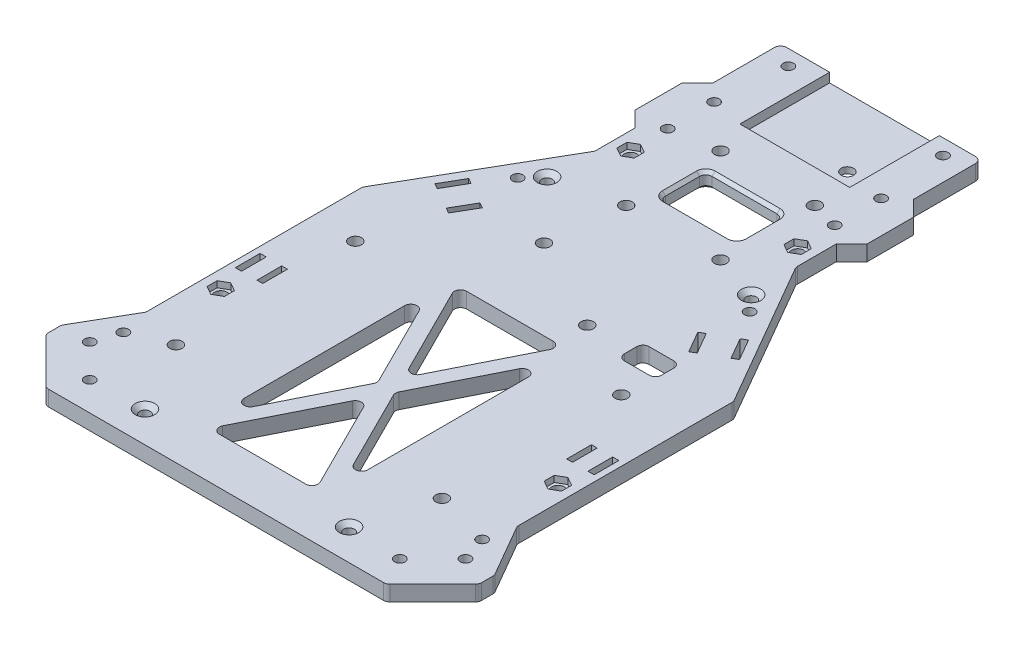
SolidWorks part; units mm, degrees
material "ABS PC"
ref_plane "Front Plane" through (0, 0, 0) normal (0, 0, 1) x (1, 0, 0)
ref_plane "Top Plane" through (0, 0, 0) normal (0, 1, 0) x (1, 0, 0)
ref_plane "Right Plane" through (0, 0, 0) normal (1, 0, 0) x (0, 0, -1)
sketch "Sketch1" plane through (0, 0, 0) normal (0, 1, 0) x (1, 0, 0)
  line L1 (70, -110) -> (-70, -110)
  line L2 (70, -110) -> (70, 110)
  line L3 (70, 110) -> (-70, 110)
  line L4 (-70, -110) -> (-70, 110)
  line L5 (70, -110) -> (-70, 110) construction
  line L6 (70, 110) -> (-70, -110) construction
  point P0 (0, 0)
  dimension "D1" = 220
  dimension "D2" = 140
extrude "Boss-Extrude1" add sketch "Sketch1" along normal blind 5
sketch "FC Mounting Holes" plane through (0, 5, 0) normal (0, 1, 0) x (1, 0, 0)
  line L0 (0, 110) -> (0, -110) construction
  line L1 (70, 110) -> (-70, 110) construction
  line L2 (-70, -110) -> (70, -110) construction
  line L4 (18.25, 65.325) -> (-12.25, 65.325) construction
  line L5 (18.25, 65.325) -> (18.25, 34.825) construction
  line L6 (18.25, 34.825) -> (-12.25, 34.825) construction
  line L7 (-12.25, 65.325) -> (-12.25, 34.825) construction
  line L8 (18.25, 65.325) -> (-12.25, 34.825) construction
  line L9 (18.25, 34.825) -> (-12.25, 65.325) construction
  point P6 (3, 50.075)
  dimension "D1" = 30.5
  dimension "D2" = 60
  dimension "D3" = 3
hole_wizard "Ø4.0 (4) Diameter Hole1" positions "Sketch3" profile "Sketch4" hole size "Ø4.0" standard "ANSI Metric" end condition through all
sketch "Sketch3" plane through (0, 5, 0) normal (0, 1, 0) x (1, 0, 0)
  point P0 (-12.25, 34.825)
  point P3 (-12.25, 65.325)
  point P6 (18.25, 65.325)
  point P9 (18.25, 34.825)
sketch "Sketch4" plane through (-12.25, 5, -34.825) normal (1, 0, 0) x (0, 0, 1)
  line L0 (0, 0) -> (0, 5)
  line L1 (0, 5) -> (2, 5)
  line L2 (2, 5) -> (2, 0)
  line L5 (2, 0) -> (0, 0)
  line L11 (0, -6.35) -> (0, 107.95) construction
  dimension "Thru Hole Dia." = 4
  dimension "Thru Hole Depth" = 5
sketch "Sketch8" plane through (0, 5, 0) normal (0, 1, 0) x (1, 0, 0)
  line L0 (-70, 110) -> (-32.5, 110)
  line L1 (70, 110) -> (-70, 110) construction
  line L2 (-32.5, 110) -> (-32.5, 44.9519)
  line L3 (-32.5, 44.9519) -> (-70, -20)
  line L4 (-70, 110) -> (-70, -110) construction
  line L5 (-70, 110) -> (-70, -20)
  line L6 (0, 110) -> (0, -110) construction
  line L7 (-70, -110) -> (70, -110) construction
  line L8 (70, 110) -> (70, -20)
  line L9 (32.5, 44.9519) -> (70, -20)
  line L10 (32.5, 110) -> (32.5, 44.9519)
  line L11 (70, 110) -> (32.5, 110)
  dimension "D1" = 130
  dimension "D2" = 30
  dimension "D3" = 65
extrude "Cut-Extrude1" cut sketch "Sketch8" against normal blind 5
chamfer "Chamfer3" distance 15 angle 45 2 edges at (70, 2.5, 110) (-70, 2.5, 110)
sketch "Sketch10" plane through (0, 0, 0) normal (0, 1, 0) x (1, 0, 0)
  line L0 (0, 110) -> (0, -110) construction
  line L1 (32.5, 110) -> (-32.5, 110) construction
  line L2 (-55, -110) -> (55, -110) construction
  line L3 (-27, 78) -> (-27, 63) construction
  line L4 (-62.5, -102.5) -> (-55.4289, -95.4289) construction
  line L5 (-60.7322, -90.1256) -> (-50.1256, -100.7322) construction
  line L6 (-70, -95) -> (-55, -110) construction
  point P9 (27, 63)
  point P10 (27, 78)
  point P17 (50.1256, -100.7322)
  point P18 (60.7322, -90.1256)
  dimension "D1" = 15
  dimension "D2" = 27
  dimension "D3" = 32
  dimension "D4" = 15
  dimension "D5" = 10
sketch "Sketch15" plane through (0, 5, 0) normal (0, 1, 0) x (1, 0, 0)
  line L0 (0, 110) -> (0, -110) construction
  line L1 (32.5, 110) -> (-32.5, 110) construction
  line L2 (-55, -110) -> (55, -110) construction
  line L3 (25, 100) -> (-25, 100) construction
  line L4 (37.5, 25) -> (-37.5, 25) construction
  line L5 (34, -50) -> (-34, -50) construction
  point P9 (0, 100)
  point P13 (0, 25)
  point P15 (0, -50)
  dimension "D1" = 50
  dimension "D2" = 10
  dimension "D3" = 75
  dimension "D4" = 85
  dimension "D5" = 68
  dimension "D6" = 160
hole_wizard "CSK for M3 Flat Head Machine Screw4" positions "Sketch16" profile "Sketch17" countersink size "M3" standard "ANSI Metric"
sketch "Sketch16" plane through (0, 0, 0) normal (0, 1, 0) x (1, 0, 0)
  point P6 (37.5, 25)
  point P9 (-37.5, 25)
  point P12 (-25, 100)
  point P15 (25, 100)
sketch "Sketch17" plane through (37.5, 0, -25) normal (1, 0, 0) x (0, 0, -1)
  line L0 (0, 0) -> (0, 6.0215)
  line L1 (0, 6.0215) -> (1.7, 5)
  line L2 (1.7, 5) -> (1.7, 1.45)
  line L3 (1.7, 1.45) -> (3.15, 0)
  line L5 (3.15, 0) -> (0, 0)
  line L6 (-1.7, 1.45) -> (-3.15, 0) construction
  line L10 (0, 6.0215) -> (-1.7, 5) construction
  line L11 (0, -6.35) -> (0, 107.95) construction
  dimension "Hole Dia." = 3.4
  dimension "Hole Depth" = 5
  dimension "Near C'Sink Dia." = 6.3
  dimension "Near C'Sink Angle" = 90
  dimension "Drill Angle" = 118
sketch "Sketch18" plane through (0, 5, 0) normal (0, 1, 0) x (1, 0, 0)
  line L0 (32.5, 110) -> (-32.5, 110) construction
  line L1 (-54.3433, 120.6104) -> (40.6659, 120.6104)
  line L2 (-54.3433, 120.6104) -> (-54.3433, 105)
  line L3 (-54.3433, 105) -> (40.6659, 105)
  line L4 (40.6659, 120.6104) -> (40.6659, 105)
  dimension "D1" = 5
extrude "Cut-Extrude2" cut sketch "Sketch18" against normal blind 5
sketch "Sketch21" plane through (0, 0, 0) normal (0, -1, 0) x (1, 0, 0)
  line L0 (3, 96.3973) -> (3, -109.7164) construction
  line L1 (-9.0168, -65.325) -> (-10.6334, -62.525)
  line L2 (-10.6334, -62.525) -> (-13.8666, -62.525)
  line L3 (-13.8666, -62.525) -> (-15.4832, -65.325)
  line L4 (-15.4832, -65.325) -> (-13.8666, -68.125)
  line L5 (-13.8666, -68.125) -> (-10.6334, -68.125)
  line L6 (-10.6334, -68.125) -> (-9.0168, -65.325)
  line L7 (-12.25, -34.825) -> (-12.25, -65.325) construction
  line L8 (-4.8959, -50.075) -> (-19.6041, -50.075) construction
  line L9 (-10.6334, -32.025) -> (-9.0168, -34.825)
  line L10 (-13.8666, -32.025) -> (-10.6334, -32.025)
  line L11 (-15.4832, -34.825) -> (-13.8666, -32.025)
  line L12 (-13.8666, -37.625) -> (-15.4832, -34.825)
  line L13 (-10.6334, -37.625) -> (-13.8666, -37.625)
  line L14 (-9.0168, -34.825) -> (-10.6334, -37.625)
  line L29 (16.6334, -68.125) -> (15.0168, -65.325)
  line L30 (19.8666, -68.125) -> (16.6334, -68.125)
  line L31 (21.4832, -65.325) -> (19.8666, -68.125)
  line L32 (19.8666, -62.525) -> (21.4832, -65.325)
  line L33 (16.6334, -62.525) -> (19.8666, -62.525)
  line L34 (15.0168, -65.325) -> (16.6334, -62.525)
  line L35 (15.0168, -34.825) -> (16.6334, -37.625)
  line L36 (16.6334, -37.625) -> (19.8666, -37.625)
  line L37 (19.8666, -37.625) -> (21.4832, -34.825)
  line L38 (21.4832, -34.825) -> (19.8666, -32.025)
  line L39 (19.8666, -32.025) -> (16.6334, -32.025)
  line L40 (16.6334, -32.025) -> (15.0168, -34.825)
  circle A0 centre (-12.25, -65.325) radius 2.8 construction
  circle A2 centre (18.25, -65.325) radius 2.8 construction
  point P17 (-12.25, -50.075)
  dimension "D1" = 5.6
  dimension "D2" = 3
extrude "Cut-Extrude5" cut sketch "Sketch21" against normal blind 2
hole_wizard "CSK for M3 Flat Head Machine Screw3" positions "Sketch29" profile "Sketch30" countersink size "M3" standard "ANSI Metric" end condition through all
sketch "Sketch29" plane through (0, 0, 0) normal (0, 1, 0) x (1, 0, 0)
  line L0 (0, -17.8468) -> (0, 28.1017) construction
  line L2 (-70, -20) -> (-70, -95) construction
  line L3 (-55, -110) -> (55, -110) construction
  point P2 (-58, -82)
  point P10 (58, -82)
  dimension "D3" = 12
  dimension "D4" = 28
sketch "Sketch30" plane through (-58, 0, 82) normal (1, 0, 0) x (0, 0, -1)
  line L0 (0, 0) -> (0, 5)
  line L1 (0, 5) -> (1.7, 5)
  line L2 (1.7, 5) -> (1.7, 1.45)
  line L3 (1.7, 1.45) -> (3.15, 0)
  line L5 (3.15, 0) -> (0, 0)
  line L6 (-1.7, 1.45) -> (-3.15, 0) construction
  line L11 (0, -6.35) -> (0, 107.95) construction
  dimension "Thru Hole Dia." = 3.4
  dimension "Thru Hole Depth" = 5
  dimension "Near C'Sink Dia." = 6.3
  dimension "Near C'Sink Angle" = 90
sketch "Sketch32" plane through (0, 0, 0) normal (0, -1, 0) x (1, 0, 0)
  line L0 (-21.5, 12) -> (-21.5, 98) construction
  line L1 (-21.5, 98) -> (21.5, 98) construction
  line L2 (21.5, 98) -> (21.5, 12) construction
  line L3 (21.5, 12) -> (-21.5, 12) construction
  line L4 (-21.5, 12) -> (21.5, 98) construction
  line L5 (-20, 55) -> (20, 55) construction
  line L6 (20, 15) -> (-20, 15)
  line L7 (20, 15) -> (20, 95)
  line L8 (20, 95) -> (-20, 95)
  line L9 (-20, 15) -> (-20, 95)
  line L10 (20, 15) -> (-20, 95) construction
  line L11 (20, 95) -> (-20, 15) construction
  line L12 (0, 15) -> (0, 95) construction
  line L13 (-20, 20.5902) -> (-2.7951, 55)
  line L14 (-17.2049, 15) -> (0, 49.4098)
  line L15 (-11.4698, 26.4703) -> (-15.9419, 28.7064)
  line L16 (-17.2049, 95) -> (0, 60.5902)
  line L17 (-20, 89.4098) -> (-2.7951, 55)
  line L18 (17.2049, 15) -> (0, 49.4098)
  line L19 (17.2049, 95) -> (0, 60.5902)
  line L20 (20, 89.4098) -> (2.7951, 55)
  line L21 (20, 20.5902) -> (2.7951, 55)
  line L22 (-55, 110) -> (55, 110) construction
  point P8 (0, 55)
  point P25 (-13.7058, 27.5883)
  dimension "D1" = 3
  dimension "D2" = 5
  dimension "D3" = 80
  dimension "D4" = 40
  dimension "D5" = 55
extrude "Cut-Extrude10" cut sketch "Sketch32" against normal through all contours L19 L8 L16 | L17 L9 L13 | L21 L7 L20 | L6 L18 L14 region at (0, 0, 26.4699) region at (14.265, 0, 55) region at (-14.265, 0, 55) region at (0, 0, 83.5301)
fillet "Fillet1" radius 2 12 edges at (20, 2.5, 89.4098) (20, 2.5, 20.5902) (2.7951, 2.5, 55) (-17.2049, 2.5, 95) (17.2049, 2.5, 95) (0, 2.5, 60.5902) (-20, 2.5, 89.4098) (-2.7951, 2.5, 55) (-20, 2.5, 20.5902) (0, 2.5, 49.4098) (17.2049, 2.5, 15) (-17.2049, 2.5, 15)
sketch "Sketch33" plane through (0, 5, 0) normal (0, 1, 0) x (1, 0, 0)
  line L1 (-46, -77) -> (40, -77)
  line L2 (-46, -77) -> (-46, -19)
  line L3 (-46, -19) -> (40, -19)
  line L4 (40, -77) -> (40, -19)
  line L5 (-46, -77) -> (40, -19) construction
  line L6 (-46, -19) -> (40, -77) construction
  point P0 (-3, -48)
  dimension "D1" = 58
  dimension "D2" = 86
  dimension "D3" = 3
  dimension "D4" = 48
hole_wizard "Ø4.0 (4) Diameter Hole8" positions "Sketch34" profile "Sketch35" hole size "Ø4.0" standard "ANSI Metric" end condition through all
sketch "Sketch34" plane through (0, 5, 0) normal (0, 1, 0) x (1, 0, 0)
  point P0 (-46, -19)
  point P3 (40, -19)
  point P6 (40, -77)
  point P9 (-46, -77)
sketch "Sketch35" plane through (-46, 5, 19) normal (1, 0, 0) x (0, 0, 1)
  line L0 (0, 0) -> (0, 5)
  line L1 (0, 5) -> (2, 5)
  line L2 (2, 5) -> (2, 0)
  line L5 (2, 0) -> (0, 0)
  line L11 (0, -6.35) -> (0, 107.95) construction
  dimension "Thru Hole Dia." = 4
  dimension "Thru Hole Depth" = 5
sketch "Sketch36" plane through (0, 5, 0) normal (0, 1, 0) x (1, 0, 0)
  line L0 (-60, -2.6795) -> (-60, -72.6795)
  line L1 (-60, -72.6795) -> (-70, -90)
  line L2 (-70, -20) -> (-70, -95) construction
  line L3 (-60, -2.6795) -> (-70, -20)
  line L4 (-70, -20) -> (-70, -90)
  line L5 (0, -68.5311) -> (0, -59.7205) construction
  line L6 (70, -20) -> (70, -90)
  line L7 (60, -2.6795) -> (70, -20)
  line L8 (60, -72.6795) -> (70, -90)
  line L9 (60, -2.6795) -> (60, -72.6795)
  line L10 (-70, -20) -> (-32.5, 44.9519) construction
  line L11 (-55, -110) -> (55, -110) construction
  dimension "D1" = 120
  dimension "D2" = 20
extrude "Cut-Extrude11" cut sketch "Sketch36" against normal blind 10
fillet "Fillet2" radius 2 14 edges at (-60, 2.5, 2.6795) (-32.5, 2.5, -44.9519) (32.5, 2.5, -105) (32.5, 2.5, -44.9519) (60, 2.5, 2.6795) (60, 2.5, 72.6795) (70, 2.5, 90) (70, 2.5, 95) (55, 2.5, 110) (-55, 2.5, 110) (-70, 2.5, 95) (-70, 2.5, 90) (-60, 2.5, 72.6795) (-32.5, 2.5, -105)
sketch "Sketch38" plane through (0, 0, 0) normal (0, -1, 0) x (1, 0, 0)
  line L0 (-49.228, -9.9781) -> (-45.228, -16.9063)
  line L1 (-45.228, -16.9063) -> (-43.496, -15.9063)
  line L2 (-43.496, -15.9063) -> (-47.496, -8.9781)
  line L3 (-47.496, -8.9781) -> (-49.228, -9.9781)
  line L4 (-59.7321, 2.2154) -> (-32.7679, -44.4878) construction
  line L5 (-60, 72.1436) -> (-60, 3.2154) construction
  line L6 (-56, 45.7891) -> (-58, 45.7891)
  line L7 (-56, 45.7891) -> (-56, 37.7891)
  line L8 (-56, 37.7891) -> (-58, 37.7891)
  line L9 (-58, 45.7891) -> (-58, 37.7891)
  line L10 (-56, 45.7891) -> (-58, 37.7891) construction
  line L11 (-56, 37.7891) -> (-58, 45.7891) construction
  line L12 (0, 63.5391) -> (0, 74.36) construction
  line L13 (58, 45.7891) -> (58, 37.7891)
  line L14 (56, 37.7891) -> (58, 37.7891)
  line L15 (56, 45.7891) -> (56, 37.7891)
  line L16 (56, 45.7891) -> (58, 45.7891)
  line L17 (47.496, -8.9781) -> (49.228, -9.9781)
  line L18 (43.496, -15.9063) -> (47.496, -8.9781)
  line L19 (45.228, -16.9063) -> (43.496, -15.9063)
  line L20 (49.228, -9.9781) -> (45.228, -16.9063)
  line L21 (-45.4114, -4.5888) -> (-39.4355, -14.9393) construction
  line L22 (-40.5678, -4.9781) -> (-38.8357, -3.9781)
  line L23 (-36.5678, -11.9063) -> (-40.5678, -4.9781)
  line L24 (-34.8357, -10.9063) -> (-36.5678, -11.9063)
  line L25 (-38.8357, -3.9781) -> (-34.8357, -10.9063)
  line L26 (38.8357, -3.9781) -> (34.8357, -10.9063)
  line L27 (34.8357, -10.9063) -> (36.5678, -11.9063)
  line L28 (36.5678, -11.9063) -> (40.5678, -4.9781)
  line L29 (40.5678, -4.9781) -> (38.8357, -3.9781)
  line L30 (51, 45.7891) -> (51, 37.7891)
  line L31 (-49.1357, 45.7891) -> (-51, 45.7891)
  line L32 (-49.1357, 45.7891) -> (-49.1357, 37.7891)
  line L33 (-49.1357, 37.7891) -> (-51, 37.7891)
  line L34 (-51, 45.7891) -> (-51, 37.7891)
  line L35 (49.1357, 37.7891) -> (51, 37.7891)
  line L36 (49.1357, 45.7891) -> (49.1357, 37.7891)
  line L37 (49.1357, 45.7891) -> (51, 45.7891)
  point P6 (-57, 41.7891)
  point P16 (57, 41.7891)
  dimension "D1" = 8
  dimension "D2" = 2
  dimension "D3" = 3
  dimension "D4" = 2
  dimension "D5" = 8
  dimension "D6" = 5
extrude "Cut-Extrude13" cut sketch "Sketch38" against normal through all
hole_wizard "CSK for M3 Flat Head Machine Screw2" positions "Sketch39" profile "Sketch40" countersink size "M3" standard "ANSI Metric" end condition through all
sketch "Sketch39" plane through (0, 5, 0) normal (0, -1, 0) x (-1, 0, 0)
  line L1 (33, 30) -> (-33, 30)
  line L2 (33, 30) -> (33, -100)
  line L3 (33, -100) -> (-33, -100)
  line L4 (-33, 30) -> (-33, -100)
  line L5 (33, 30) -> (-33, -100) construction
  line L6 (33, -100) -> (-33, 30) construction
  line L7 (0, -35) -> (0, 0) construction
  point P2 (-33, -100)
  point P5 (33, 30)
  point P6 (33, -100)
  point P7 (-33, 30)
  dimension "D1" = 66
  dimension "D2" = 130
  dimension "D3" = 35
sketch "Sketch40" plane through (33, 5, 100) normal (1, 0, 0) x (0, 0, 1)
  line L0 (0, 0) -> (0, 5)
  line L1 (0, 5) -> (1.7, 5)
  line L2 (1.7, 5) -> (1.7, 1.45)
  line L3 (1.7, 1.45) -> (3.15, 0)
  line L5 (3.15, 0) -> (0, 0)
  line L6 (-1.7, 1.45) -> (-3.15, 0) construction
  line L11 (0, -6.35) -> (0, 107.95) construction
  dimension "Thru Hole Dia." = 3.4
  dimension "Thru Hole Depth" = 5
  dimension "Near C'Sink Dia." = 6.3
  dimension "Near C'Sink Angle" = 90
sketch "Sketch41" plane through (0, 5, 0) normal (0, -1, 0) x (1, 0, 0)
  line L0 (-30.5, -105) -> (30.5, -105) construction
  line L1 (-16.65, -76) -> (18.85, -76)
  line L2 (-16.65, -76) -> (-16.65, -105)
  line L3 (-16.65, -105) -> (18.85, -105)
  line L4 (18.85, -76) -> (18.85, -105)
  line L5 (-16.65, -76) -> (18.85, -105) construction
  line L6 (-16.65, -105) -> (18.85, -76) construction
  line L10 (0, -105) -> (0, -72.8901) construction
  point P0 (1.1, -90.5)
  dimension "D1" = 35.5
  dimension "D2" = 29
  dimension "D3" = 1.1
extrude "Cut-Extrude14" cut sketch "Sketch41" along normal blind 3
hole_wizard "Ø4.0 (4) Diameter Hole10" positions "Sketch43" profile "Sketch44" hole size "Ø4.0" standard "ANSI Metric"
sketch "Sketch43" plane through (0, 0, 0) normal (0, -1, 0) x (-1, 0, 0)
  line L3 (30.5, 105) -> (-30.5, 105) construction
  line L5 (0, 112.2208) -> (0, 95.513) construction
  point P0 (-11.1, 83)
  dimension "D1" = 22
  dimension "D2" = 11.1
sketch "Sketch44" plane through (11.1, 0, -83) normal (1, 0, 0) x (0, 0, -1)
  line L0 (0, 0) -> (0, 11.2017)
  line L1 (0, 11.2017) -> (2, 10)
  line L2 (2, 10) -> (2, 0)
  line L5 (2, 0) -> (0, 0)
  line L10 (0, 11.2017) -> (-2, 10) construction
  line L11 (0, -6.35) -> (0, 107.95) construction
  dimension "Hole Dia." = 4
  dimension "Hole Depth" = 10
  dimension "Drill Angle" = 118
hole_wizard "Ø4.0 (4) Diameter Hole11" positions "Sketch47" profile "Sketch48" hole size "Ø4.0" standard "ANSI Metric"
sketch "Sketch47" plane through (0, 5, 0) normal (0, 1, 0) x (1, 0, 0)
  line L1 (-15, -5) -> (15, -5)
  line L2 (-15, -5) -> (-15, 11)
  line L3 (-15, 11) -> (15, 11)
  line L4 (15, -5) -> (15, 11)
  line L5 (-15, -5) -> (15, 11) construction
  line L6 (-15, 11) -> (15, -5) construction
  line L7 (0, 3) -> (0, 0) construction
  point P5 (-15, 11)
  point P6 (15, -5)
  dimension "D1" = 30
  dimension "D2" = 16
  dimension "D3" = 3
sketch "Sketch48" plane through (15, 5, 5) normal (1, 0, 0) x (0, 0, 1)
  line L0 (0, 0) -> (0, 11.2017)
  line L1 (0, 11.2017) -> (2, 10)
  line L2 (2, 10) -> (2, 0)
  line L5 (2, 0) -> (0, 0)
  line L10 (0, 11.2017) -> (-2, 10) construction
  line L11 (0, -6.35) -> (0, 107.95) construction
  dimension "Hole Dia." = 4
  dimension "Hole Depth" = 10
  dimension "Drill Angle" = 118
sketch "Sketch49" plane through (0, 0, 0) normal (0, -1, 0) x (1, 0, 0)
  line L1 (-11.7668, -11) -> (-13.3834, -8.2)
  line L2 (-13.3834, -8.2) -> (-16.6166, -8.2)
  line L3 (-16.6166, -8.2) -> (-18.2332, -11)
  line L4 (-18.2332, -11) -> (-16.6166, -13.8)
  line L5 (-16.6166, -13.8) -> (-13.3834, -13.8)
  line L6 (-13.3834, -13.8) -> (-11.7668, -11)
  line L7 (18.2332, 5) -> (16.6166, 7.8)
  line L8 (16.6166, 7.8) -> (13.3834, 7.8)
  line L9 (13.3834, 7.8) -> (11.7668, 5)
  line L10 (11.7668, 5) -> (13.3834, 2.2)
  line L11 (13.3834, 2.2) -> (16.6166, 2.2)
  line L12 (16.6166, 2.2) -> (18.2332, 5)
  circle A0 centre (-15, -11) radius 2.8 construction
  circle A1 centre (15, 5) radius 2.8 construction
  dimension "D1" = 5.6
extrude "Cut-Extrude15" cut sketch "Sketch49" against normal blind 2
hole_wizard "Ø4.0 (4) Diameter Hole12" positions "Sketch50" profile "Sketch51" hole size "Ø4.0" standard "ANSI Metric" end condition through all
sketch "Sketch50" plane through (0, 5, 0) normal (0, 1, 0) x (1, 0, 0)
  line L0 (18.85, 105) -> (30.5, 105) construction
  line L1 (32.5, 103) -> (32.5, 45.4878) construction
  line L2 (60, -3.2154) -> (60, -72.1436) construction
  point P0 (27, 51)
  point P2 (54.5, -54)
  dimension "D1" = 54
  dimension "D2" = 5.5
  dimension "D3" = 105
  dimension "D4" = 5.5
sketch "Sketch51" plane through (27, 5, -51) normal (1, 0, 0) x (0, 0, 1)
  line L0 (0, 0) -> (0, 5)
  line L1 (0, 5) -> (2, 5)
  line L2 (2, 5) -> (2, 0)
  line L5 (2, 0) -> (0, 0)
  line L11 (0, -6.35) -> (0, 107.95) construction
  dimension "Thru Hole Dia." = 4
  dimension "Thru Hole Depth" = 5
mirror "Mirror1" about plane through (0, 0, 0) normal (1, 0, 0) of "Ø4.0 (4) Diameter Hole12"
sketch "Sketch52" plane through (0, 5, 0) normal (0, 1, 0) x (1, 0, 0)
  line L0 (32.5, 103) -> (32.5, 45.4878) construction
  line L1 (29.8, 49.3834) -> (29.8, 52.6166)
  line L2 (29.8, 52.6166) -> (27, 54.2332)
  line L3 (27, 54.2332) -> (24.2, 52.6166)
  line L4 (24.2, 52.6166) -> (24.2, 49.3834)
  line L5 (24.2, 49.3834) -> (27, 47.7668)
  line L6 (27, 47.7668) -> (29.8, 49.3834)
  line L7 (60, -3.2154) -> (60, -72.1436) construction
  line L8 (57.3, -55.6166) -> (57.3, -52.3834)
  line L9 (57.3, -52.3834) -> (54.5, -50.7668)
  line L10 (54.5, -50.7668) -> (51.7, -52.3834)
  line L11 (51.7, -52.3834) -> (51.7, -55.6166)
  line L12 (51.7, -55.6166) -> (54.5, -57.2332)
  line L13 (54.5, -57.2332) -> (57.3, -55.6166)
  line L14 (0, 31.2667) -> (0, -10.4879) construction
  line L15 (-54.5, -57.2332) -> (-57.3, -55.6166)
  line L16 (-51.7, -55.6166) -> (-54.5, -57.2332)
  line L17 (-51.7, -52.3834) -> (-51.7, -55.6166)
  line L18 (-54.5, -50.7668) -> (-51.7, -52.3834)
  line L19 (-57.3, -52.3834) -> (-54.5, -50.7668)
  line L20 (-57.3, -55.6166) -> (-57.3, -52.3834)
  line L21 (-27, 47.7668) -> (-29.8, 49.3834)
  line L22 (-24.2, 49.3834) -> (-27, 47.7668)
  line L23 (-24.2, 52.6166) -> (-24.2, 49.3834)
  line L24 (-27, 54.2332) -> (-24.2, 52.6166)
  line L25 (-29.8, 52.6166) -> (-27, 54.2332)
  line L26 (-29.8, 49.3834) -> (-29.8, 52.6166)
  circle A0 centre (27, 51) radius 2.8 construction
  circle A1 centre (54.5, -54) radius 2.8 construction
  circle A2 centre (-54.5, -54) radius 2.8 construction
  circle A3 centre (-27, 51) radius 2.8 construction
  dimension "D1" = 5.6
extrude "Cut-Extrude16" cut sketch "Sketch52" against normal blind 2
hole_wizard "CSK for M3 Flat Head Machine Screw1" positions "Sketch53" profile "Sketch54" countersink size "M3" standard "ANSI Metric"
sketch "Sketch53" plane through (0, 0, 0) normal (0, -1, 0) x (-1, 0, 0)
  point P0 (27, 78)
  point P3 (27, 63)
  point P6 (-27, 63)
  point P9 (-27, 78)
  point P12 (50.1256, -100.7322)
  point P15 (60.7322, -90.1256)
  point P18 (-50.1256, -100.7322)
  point P21 (-60.7322, -90.1256)
sketch "Sketch54" plane through (-27, 0, -78) normal (1, 0, 0) x (0, 0, -1)
  line L0 (0, 0) -> (0, 6.0215)
  line L1 (0, 6.0215) -> (1.7, 5)
  line L2 (1.7, 5) -> (1.7, 1.45)
  line L3 (1.7, 1.45) -> (3.15, 0)
  line L5 (3.15, 0) -> (0, 0)
  line L6 (-1.7, 1.45) -> (-3.15, 0) construction
  line L10 (0, 6.0215) -> (-1.7, 5) construction
  line L11 (0, -6.35) -> (0, 107.95) construction
  dimension "Hole Dia." = 3.4
  dimension "Hole Depth" = 5
  dimension "Near C'Sink Dia." = 6.3
  dimension "Near C'Sink Angle" = 90
  dimension "Drill Angle" = 118
sketch "Sketch45" plane through (0, 5, 0) normal (0, 1, 0) x (1, 0, 0)
  line L0 (-27, 78) -> (-27, 63) construction
  line L1 (-27, 70.5) -> (-37.5, 70.5) construction
  line L2 (-37.5, 63) -> (-37.5, 78)
  line L3 (-37.5, 78) -> (-32.5, 83)
  line L4 (-32.5, 45.4878) -> (-32.5, 103) construction
  line L5 (-32.5, 83) -> (-32.5, 58)
  line L6 (-37.5, 63) -> (-32.5, 58)
  line L7 (0, 66.854) -> (0, 57.1488) construction
  line L8 (37.5, 63) -> (32.5, 58)
  line L9 (32.5, 83) -> (32.5, 58)
  line L10 (37.5, 78) -> (32.5, 83)
  line L11 (37.5, 63) -> (37.5, 78)
  point P12 (-32.5, 70.5)
  point P16 (32.5, 70.5)
  dimension "D1" = 5
  dimension "D2" = 45
  dimension "D3" = 25
extrude "Boss-Extrude2" add sketch "Sketch45" against normal through all
sketch "Sketch55" plane through (0, 0, 0) normal (0, -1, 0) x (1, 0, 0)
  line L0 (-3, 23.8086) -> (-3, 33.1271) construction
  line L1 (37.2, 17.3834) -> (37.2, 20.6166)
  line L2 (-42.7668, 77) -> (-44.3834, 79.8)
  line L3 (-44.3834, 79.8) -> (-47.6166, 79.8)
  line L4 (-47.6166, 79.8) -> (-49.2332, 77)
  line L5 (-49.2332, 77) -> (-47.6166, 74.2)
  line L6 (-47.6166, 74.2) -> (-44.3834, 74.2)
  line L7 (-44.3834, 74.2) -> (-42.7668, 77)
  line L8 (-43.2, 20.6166) -> (-46, 22.2332)
  line L9 (-46, 22.2332) -> (-48.8, 20.6166)
  line L10 (-48.8, 20.6166) -> (-48.8, 17.3834)
  line L11 (-48.8, 17.3834) -> (-46, 15.7668)
  line L12 (-46, 15.7668) -> (-43.2, 17.3834)
  line L13 (-43.2, 17.3834) -> (-43.2, 20.6166)
  line L14 (40, 15.7668) -> (37.2, 17.3834)
  line L15 (42.8, 17.3834) -> (40, 15.7668)
  line L16 (42.8, 20.6166) -> (42.8, 17.3834)
  line L17 (40, 22.2332) -> (42.8, 20.6166)
  line L18 (37.2, 20.6166) -> (40, 22.2332)
  line L19 (38.3834, 74.2) -> (36.7668, 77)
  line L20 (41.6166, 74.2) -> (38.3834, 74.2)
  line L21 (43.2332, 77) -> (41.6166, 74.2)
  line L22 (41.6166, 79.8) -> (43.2332, 77)
  line L23 (38.3834, 79.8) -> (41.6166, 79.8)
  line L24 (36.7668, 77) -> (38.3834, 79.8)
  line L25 (-60, 72.1436) -> (-60, 3.2154) construction
  line L26 (-69.7321, 89.5359) -> (-60.2679, 73.1436) construction
  circle A0 centre (-46, 77) radius 2.8 construction
  circle A1 centre (-46, 19) radius 2.8 construction
  circle A2 centre (40, 19) radius 2.8 construction
  circle A3 centre (40, 77) radius 2.8 construction
  dimension "D1" = 5.6
  dimension "D2" = 3
extrude "Cut-Extrude17" cut sketch "Sketch55" against normal blind 2
sketch "Sketch56" plane through (0, 5, 0) normal (0, 1, 0) x (1, 0, 0)
  line L0 (-12.25, 65.325) -> (18.25, 65.325) construction
  line L1 (3, 65.325) -> (3, 50.325) construction
  line L3 (-9.5, 42.825) -> (15.5, 42.825)
  line L4 (-9.5, 42.825) -> (-9.5, 57.825)
  line L5 (-9.5, 57.825) -> (15.5, 57.825)
  line L6 (15.5, 42.825) -> (15.5, 57.825)
  line L7 (-9.5, 42.825) -> (15.5, 57.825) construction
  line L8 (-9.5, 57.825) -> (15.5, 42.825) construction
  dimension "D1" = 25
  dimension "D2" = 15
  dimension "D3" = 15
extrude "Cut-Extrude18" cut sketch "Sketch56" against normal through all
fillet "Fillet3" radius 2 4 edges at (-9.5, 2.5, -42.825) (15.5, 2.5, -57.825) (15.5, 2.5, -42.825) (-9.5, 2.5, -57.825)
chamfer "Chamfer5" distance 1 angle 45 16 edges at (3, 5, -42.825) (14.9142, 5, -43.4108) (-8.9142, 5, -43.4108) (15.5, 5, -50.325) (-9.5, 5, -50.325) (14.9142, 5, -57.2393) (-8.9142, 5, -57.2393) (3, 5, -57.825) (3, 0, -42.825) (14.9142, 0, -43.4108) (-8.9142, 0, -43.4108) (15.5, 0, -50.325) (-9.5, 0, -50.325) (14.9142, 0, -57.2393) (-8.9142, 0, -57.2393) (3, 0, -57.825)
sketch "Sketch57" plane through (0, 5, 0) normal (0, 1, 0) x (1, 0, 0)
  line L0 (60, -3.2154) -> (60, -72.1436) construction
  line L1 (29, -9) -> (41, -9)
  line L2 (29, -9) -> (29, -1)
  line L3 (29, -1) -> (41, -1)
  line L4 (41, -9) -> (41, -1)
  line L5 (29, -9) -> (41, -1) construction
  line L6 (29, -1) -> (41, -9) construction
  line L7 (18.85, 105) -> (30.5, 105) construction
  point P0 (35, -5)
  dimension "D1" = 12
  dimension "D2" = 8
  dimension "D3" = 25
  dimension "D4" = 110
extrude "Cut-Extrude19" cut sketch "Sketch57" against normal through all
fillet "Fillet4" radius 2 4 edges at (29, 2.5, 9) (41, 2.5, 1) (41, 2.5, 9) (29, 2.5, 1)
